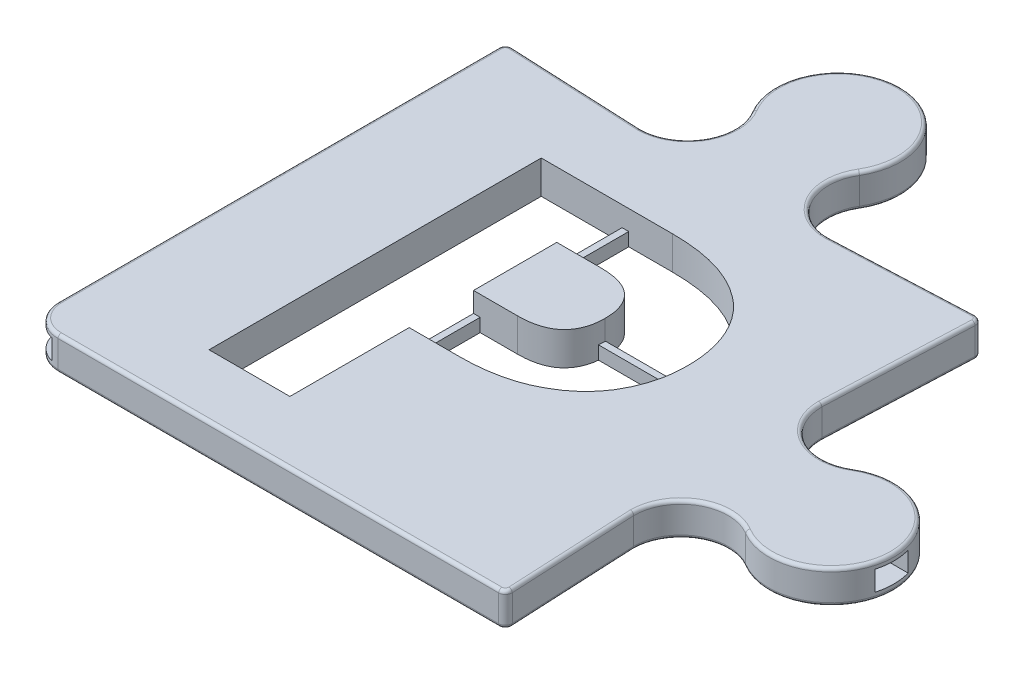
SolidWorks part; units mm, degrees
ref_plane "Front Plane" through (0, 0, 0) normal (0, 0, 1) x (1, 0, 0)
ref_plane "Top Plane" through (0, 0, 0) normal (0, 1, 0) x (1, 0, 0)
ref_plane "Right Plane" through (0, 0, 0) normal (1, 0, 0) x (0, 0, -1)
sketch "Sketch1" plane through (0, 0, 0) normal (0, 1, 0) x (1, 0, 0)
  line L0 (-31, -36) -> (37, -36) construction
  line L1 (-36, 37) -> (-36, -31) construction
  line L2 (-14.1421, 36) -> (-36, 37) construction
  line L3 (37, 37) -> (14.1421, 36) construction
  line L4 (36, 13.1421) -> (37, 37) construction
  line L5 (37, -36) -> (36, -15.1421) construction
  line L6 (-35.4, 36.3719) -> (-35.4, -31)
  line L7 (-36, 36) -> (36, 36) construction
  line L8 (-36, 36) -> (-36, -36) construction
  line L9 (-36, -36) -> (36, -36) construction
  line L10 (36, 36) -> (36, -36) construction
  line L11 (-31, -35.4) -> (36.3705, -35.4)
  line L12 (36.3705, -35.4) -> (35.4, -15.1568)
  line L13 (35.4, 13.155) -> (36.3732, 36.372)
  line L14 (36.3732, 36.372) -> (14.1555, 35.4)
  line L15 (-14.1562, 35.4) -> (-35.4, 36.3719)
  line L16 (-30, -24) -> (30, -24) construction
  line L17 (-30, 29) -> (30, 29) construction
  line L18 (-30, 29) -> (-30, -31) construction
  line L19 (-30, -31) -> (30, -31) construction
  line L20 (30, 29) -> (30, -31) construction
  line L21 (-30, 24) -> (30, 24) construction
  line L22 (-30, 24) -> (-30, -26) construction
  line L23 (-30, -26) -> (30, -26) construction
  line L24 (30, 24) -> (30, -26) construction
  arc A0 (-36, -31) -> (-31, -36) centre (-31, -31) ccw construction
  arc A1 (-14.1421, 36) -> (-8.571, 45.8485) centre (-14.1421, 42.5) ccw construction
  arc A2 (8.571, 45.8485) -> (-8.571, 45.8485) centre (0, 51) ccw construction
  arc A3 (8.571, 45.8485) -> (14.1421, 36) centre (14.1421, 42.5) ccw construction
  arc A4 (36, 13.1421) -> (45.8485, 7.571) centre (42.5, 13.1421) ccw construction
  arc A5 (45.8485, -9.571) -> (45.8485, 7.571) centre (51, -1) ccw construction
  arc A6 (45.8485, -9.571) -> (36, -15.1421) centre (42.5, -15.1421) ccw construction
  arc A7 (-35.4, -31) -> (-31, -35.4) centre (-31, -31) ccw
  arc A8 (46.1576, -9.0567) -> (35.4, -15.1568) centre (42.5, -15.1421) ccw
  arc A9 (46.1576, -9.0567) -> (46.1576, 7.0567) centre (51, -1) ccw
  arc A10 (35.4, 13.155) -> (46.1576, 7.0567) centre (42.5, 13.1421) ccw
  arc A11 (8.0567, 46.1576) -> (14.1555, 35.4) centre (14.1421, 42.5) ccw
  arc A12 (8.0567, 46.1576) -> (-8.0567, 46.1576) centre (0, 51) ccw
  arc A13 (-14.1562, 35.4) -> (-8.0567, 46.1576) centre (-14.1421, 42.5) ccw
  point P32 (36, 0)
  point P34 (0, 36)
  dimension "D5" = 6.5
  dimension "D6" = 10
  dimension "D7" = 6.5
  dimension "D13" = 5
  dimension "D9" = 10
  dimension "D11" = 6.5
  dimension "D12" = 6.5
  dimension "D1" = 72
  dimension "D2" = 1
  dimension "D3" = 1
  dimension "D4" = 15
  dimension "D8" = 1
  dimension "D10" = 35
  dimension "D14" = 15
  dimension "D15" = 36
  dimension "D16" = 1
  dimension "D18" = 60
  dimension "D19" = 60
  dimension "D20" = 5
  dimension "D21" = 6
  dimension "D22" = 5
  dimension "D23" = 50
  dimension "D24" = 2
  dimension "D17" = 0.6
extrude "Boss-Extrude1" add sketch "Sketch1" along normal blind 5
sketch "Sketch6" plane through (0, 0, 0) normal (0, -1, 0) x (1, 0, 0)
  line L0 (-35.4, -36.3719) -> (-35.4, 31) construction
  line L1 (-35.4, 17.9) -> (-27.4, 17.9)
  line L2 (-35.4, 17.9) -> (-35.4, -16.1)
  line L3 (-35.4, -16.1) -> (-27.4, -16.1)
  line L4 (-27.4, 17.9) -> (-27.4, -16.1)
  line L5 (-31, 35.4) -> (36.3705, 35.4) construction
  line L6 (-35.4, 14.65) -> (-30.4, 14.65)
  line L7 (-35.4, 14.65) -> (-35.4, -12.85)
  line L8 (-35.4, -12.85) -> (-30.4, -12.85)
  line L9 (-30.4, 14.65) -> (-30.4, -12.85)
  point P15 (-27.4, 0.9)
  point P16 (-30.4, 0.9)
  line M28 (-35.4, 31) -> (-35.4, -36.3719)
  dimension "D1" = 8
  dimension "D2" = 20.75
  dimension "D3" = 27.5
  dimension "D4" = 5
  dimension "D5" = 34
extrude "Cut-Extrude3" cut sketch "Sketch6" against normal blind 3 from offset 1 contours L6 L9 L8 L3 L4 L1 M28 | L9 L6 L2 L8 region at (-29.8665, 0, 0.9) region at (-32.9, 0, 0.9) offset against normal yes
extrude "Cut-Extrude4" cut sketch "Sketch6<3>" against normal up to next contours L9 L6 L2 L8 region at (-32.9, 0, 0.9)
sketch "Sketch6<3>" plane through (0, 0, 0) normal (0, -1, 0) x (1, 0, 0) same geometry as "Sketch6"
sketch "Sketch8" plane through (0, 0, 0) normal (0, -1, 0) x (1, 0, 0)
  line L1 (-2.5, -51.4) -> (2.5, -51.4)
  line L2 (-2.5, -51.4) -> (-2.5, -60.4)
  line L3 (-2.5, -60.4) -> (2.5, -60.4)
  line L4 (2.5, -51.4) -> (2.5, -60.4)
  line L5 (51.4, 3.5) -> (60.4, 3.5)
  line L6 (51.4, 3.5) -> (51.4, -1.5)
  line L7 (51.4, -1.5) -> (60.4, -1.5)
  line L8 (60.4, 3.5) -> (60.4, -1.5)
  arc A0 (-8.0567, -46.1576) -> (8.0567, -46.1576) centre (0, -51) ccw construction
  arc A1 (46.1576, -7.0567) -> (46.1576, 9.0567) centre (51, 1) ccw construction
  point P4 (0, -60.4)
  point P13 (60.4, 1)
  dimension "D1" = 5
  dimension "D2" = 9
  dimension "D3" = 5
  dimension "D4" = 9
extrude "Cut-Extrude5" cut sketch "Sketch8" against normal blind 3 from offset 1 offset against normal yes
sketch "Sketch9" plane through (0, 0, 0) normal (0, -1, 0) x (1, 0, 0)
  line L0 (-31, 35.4) -> (36.3705, 35.4) construction
  line L1 (-35.4, 14.65) -> (-35.4, 31) construction
  line L2 (-31.7636, 35.3332) -> (-35.4, 31) construction
  line L3 (-33.2571, 29.735) -> (-30.0429, 33.565) construction
  line L4 (-30.0429, 33.565) -> (-33.2571, 29.735) construction
  line L5 (-30.0429, 33.565) -> (-32.7119, 35.8048)
  line L6 (-33.2571, 29.735) -> (-35.926, 31.9747)
  line L7 (-32.7119, 35.8048) -> (-35.926, 31.9747)
  circle A0 centre (-31.65, 31.65) radius 2.5
  arc A1 (-31, 35.4) -> (-35.4, 31) centre (-31, 31) ccw construction
  arc M41 (-31, 35.4) -> (-35.4, 31) centre (-31, 31) ccw
  dimension "D1" = 5
  dimension "D3" = 3.75
  dimension "D4" = 5.6569
  dimension "D2" = 3.75
extrude "Cut-Extrude6" cut sketch "Sketch9" against normal blind 3 from offset 1 contours A0 L5 L6 M41 | A0 L5 region at (-33.6239, 0, 33.3064) region at (-31.65, 0, 31.65) offset against normal yes
sketch "Sketch11" plane through (-35.4, 0, 0) normal (-1, 0, 0) x (0, 0, 1)
  line L0 (-13.155, 0) -> (-36.372, 0) construction
  line L1 (-25.1, 3) -> (-19.1, 3)
  line L2 (-25.1, 3) -> (-25.1, 1.5)
  line L3 (-25.1, 1.5) -> (-19.1, 1.5)
  line L4 (-19.1, 3) -> (-19.1, 1.5)
  line L5 (-16.1, 4) -> (-16.1, 1) construction
  line L6 (35.4, 0) -> (15.1568, 0) construction
  line L7 (20.9, 3) -> (26.9, 3)
  line L8 (20.9, 3) -> (20.9, 1.5)
  line L9 (20.9, 1.5) -> (26.9, 1.5)
  line L10 (26.9, 3) -> (26.9, 1.5)
  line L12 (17.9, 4) -> (17.9, 1) construction
  dimension "D1" = 3
  dimension "D2" = 1.5
  dimension "D3" = 3
  dimension "D4" = 6
  dimension "D5" = 3
  dimension "D6" = 1.5
  dimension "D7" = 6
  dimension "D8" = 3
fillet "Fillet1" radius 0.5 17 edges at (-35.4, 0, 22.825) (-34.1113, 0, 34.1113) (2.6853, 0, 35.4) (35.8853, 0, 25.2784) (38.9978, 0, 8.966) (60.4, 0, 1) (38.9986, 0, -6.9655) (35.8866, 0, -24.7635) (25.2643, 0, -35.886) (7.9657, 0, -38.9984) (0, 0, -60.4) (-7.9658, 0, -38.9981) (-24.7781, 0, -35.886) (-35.4, 0, -24.611) (-32.9, 0, -12.85) (-30.4, 0, 0.9) (-32.9, 0, 14.65)
fillet "Fillet2" radius 0.5 13 edges at (-7.9658, 5, -38.9981) (0, 5, -60.4) (7.9657, 5, -38.9984) (25.2643, 5, -35.886) (35.8866, 5, -24.7635) (38.9986, 5, -6.9655) (60.4, 5, 1) (38.9978, 5, 8.966) (35.8853, 5, 25.2784) (2.6853, 5, 35.4) (-34.1113, 5, 34.1113) (-35.4, 5, -2.686) (-24.7781, 5, -35.886)
fillet "Fillet3" radius 1 9 edges at (36.2202, 0.1464, -36.2187) (36.2202, 4.8536, -36.2187) (36.3732, 2.5, -36.372) (-35.2536, 0.1464, -36.2186) (-35.2536, 4.8536, -36.2186) (36.2169, 0.1464, 35.2536) (36.2169, 4.8536, 35.2536) (36.3705, 2.5, 35.4) (-35.4, 2.5, -36.3719)
extrude "Cut-Extrude9" cut sketch "Sketch11" against normal blind 3
chamfer "Chamfer1" distance 1 angle 50 2 edges at (-35.4, 1.5, 23.9) (-35.4, 1.5, -22.1) first distance on face at (-35.4, 2.25, -22.1)
sketch "Sketch12" plane through (0, 5, 0) normal (0, 1, 0) x (1, 0, 0)
  text T0 "P" font "Poppins" height 50
extrude "Cut-Extrude10" cut sketch "Sketch12" against normal through all
sketch "Sketch13" plane through (0, 0, 0) normal (0, -1, 0) x (1, 0, 0)
  line L0 (-17.6731, -24) -> (2.0507, -24) construction
  line L1 (-5.5029, 8.0486) -> (-4.5029, 8.0486)
  line L2 (-5.5029, 8.0486) -> (-5.5029, -24)
  line L3 (-5.5029, -24) -> (-4.5029, -24)
  line L4 (-4.5029, 8.0486) -> (-4.5029, -24)
  line L5 (2.0507, 8.0486) -> (-5.5029, 8.0486) construction
  line L6 (5.2591, -6.9514) -> (24.1817, -6.9514)
  line L7 (5.2591, -6.9514) -> (5.2591, -7.9514)
  line L8 (5.2591, -7.9514) -> (24.1817, -7.9514)
  line L9 (24.1817, -6.9514) -> (24.1817, -7.9514)
  line L10 (-5.5029, 8.0486) -> (-5.5029, 26) construction
  line L11 (-17.6731, 26) -> (-5.5029, 26)
  line L12 (-17.6731, 26) -> (-17.6731, 25)
  line L13 (-17.6731, 25) -> (-5.5029, 25)
  line L14 (-5.5029, 26) -> (-5.5029, 25)
  dimension "D1" = 1
  dimension "D2" = 1
  dimension "D3" = 15
  dimension "D4" = 18.9226
  dimension "D5" = 10.762
  dimension "D6" = 1
extrude "Boss-Extrude2" add sketch "Sketch13" against normal blind 2
